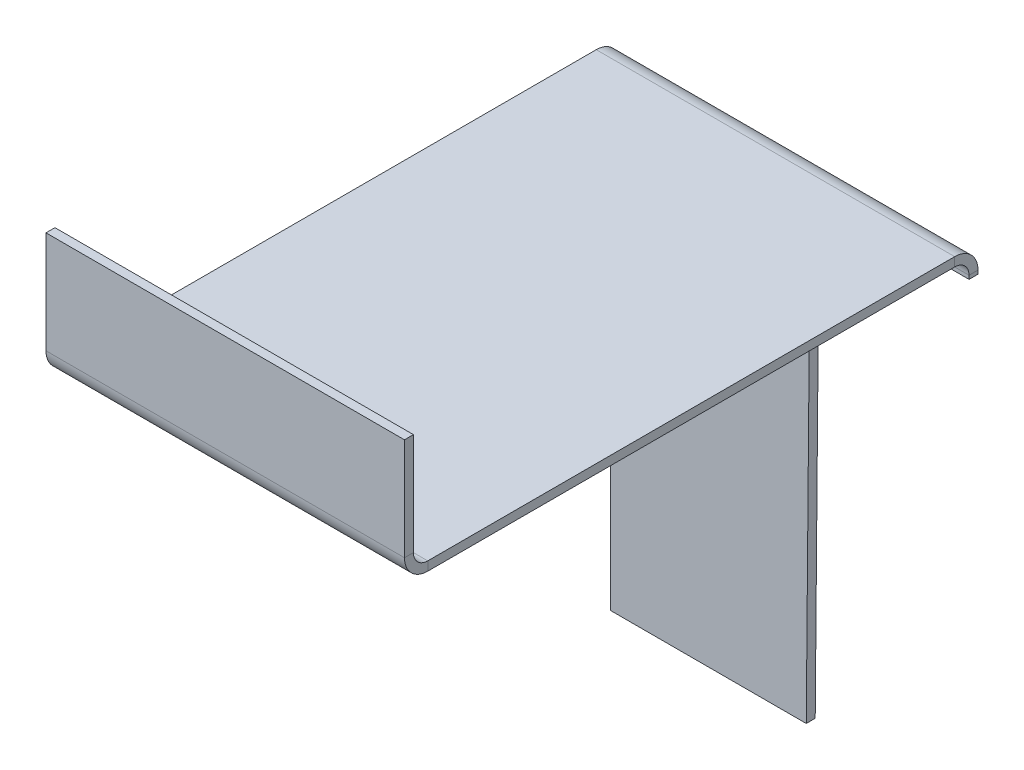
SolidWorks part; units mm, degrees
note: The reader was unsure of these and kept them because the rebuilt part matched: flange length of "Edge-Flange1", "Edge-Flange2".
material "Plain Carbon Steel"
ref_plane "Front Plane" through (0, 0, 0) normal (0, 0, 1) x (1, 0, 0)
ref_plane "Top Plane" through (0, 0, 0) normal (0, 1, 0) x (1, 0, 0)
ref_plane "Right Plane" through (0, 0, 0) normal (1, 0, 0) x (0, 0, -1)
sketch "Sketch1" plane through (0, 0, 0) normal (0, 0, 1) x (1, 0, 0)
  line L0 (0, 0) -> (0, 3)
  line L1 (0, 3) -> (-40, 3)
  line L2 (0, 0) -> (-17.7, 0)
  line L3 (-17.7, 0) -> (-18.1651, -52)
  line L4 (-40, 3) -> (-40, -52)
  line L5 (-40, -52) -> (-18.1651, -52)
  dimension "D1" = 3
  dimension "D2" = 40
  dimension "D3" = 17.7
  dimension "D4" = 55
base flange "Base-Flange1" sketch "Sketch1" thickness 1 reverse thickness direction no parameters "D1"=1.6
edge flange "Edge-Flange1" sketch "Sketch8" flange angle 90 flange length 64 flange position material inside bend radius 1.6 thickness 1 relief rectangular parameters "D6"=10
sketch "Sketch8" plane through (0, 3, 0) normal (0, 1, 0) x (-1, 0, 0)
  line L0 (0, 0) -> (40, 0) construction
  line L1 (0, 0) -> (40, 0)
  line L2 (0, 0) -> (0, 63)
  line L3 (0, 63) -> (40, 63)
  line L4 (40, 63) -> (40, 0)
bend "EdgeBend1" bend radius 1.6 bend angle 90 parameters "D5"=1
edge flange "Edge-Flange2" sketch "Sketch11" flange angle 90 flange length 14 flange position material inside bend radius 1.6 thickness 1 relief rectangular parameters "D6"=10
sketch "Sketch11" plane through (0, 3, 63) normal (0, 0, 1) x (1, 0, 0)
  line L0 (-40, 0) -> (0, 0) construction
  line L1 (-40, 0) -> (0, 0)
  line L2 (-40, 0) -> (-40, 13)
  line L3 (-40, 13) -> (0, 13)
  line L4 (0, 13) -> (0, 0)
bend "EdgeBend2" bend radius 1.6 bend angle 90 parameters "D5"=2
sketch "Bend-Lines1" [suppressed] plane through (0, 0, 0) normal (0, 1, 0) x (1, 0, 0)
sketch "Bounding-Box1" [suppressed] plane through (0, 0, 0) normal (0, 1, 0) x (1, 0, 0)
sheet metal parameters "Sheet-Metal8" thickness 1 parameters "D1"=1.6
flat pattern "Flat-Pattern8" [suppressed]
sketch "Bend-Lines2" plane through (0, 0, 0) normal (0, 1, 0) x (1, 0, 0)
sketch3d "Bounding-Box2" [suppressed]
  line L0 (0, 3, 0) -> (0, -52, 0) construction
  line L1 (40, 3, 0) -> (40, -52, 0) construction
  line L2 (0, 3, 0) -> (40, 3, 0) construction
  line L3 (0, -52, 0) -> (40, -52, 0) construction
sheet metal parameters "Sheet-Metal9" thickness 1 parameters "D1"=1.6
flat pattern "Flat-Pattern8"
sketch "Bend-Lines2" plane through (0, 0, 0) normal (0, 0, 1) x (1, 0, 0)
  line L0 (0, 2.0493) -> (-40, 2.0493) construction
  line L1 (0, 2.0493) -> (-40, 2.0493) construction
sketch3d "Bounding-Box2" [suppressed]
  line L0 (0, 65.0987, 0) -> (0, -52, 0) construction
  line L1 (-40, 65.0987, 0) -> (-40, -52, 0) construction
  line L2 (0, 65.0987, 0) -> (-40, 65.0987, 0) construction
  line L3 (0, -52, 0) -> (-40, -52, 0) construction
bend of the flat pattern "Flatten-<EdgeBend1>1"
sheet metal parameters "Sheet-Metal10" thickness 1 parameters "D1"=1.6
flat pattern "Flat-Pattern8"
sketch "Bend-Lines2" plane through (0, 0, 0) normal (0, 0, 1) x (1, 0, 0)
  line L0 (0, 2.0493) -> (-40, 2.0493) construction
  line L1 (0, 2.0493) -> (-40, 2.0493) construction
  line L2 (0, 64.148) -> (-40, 64.148) construction
  line L3 (0, 64.148) -> (-40, 64.148) construction
sketch3d "Bounding-Box2" [suppressed]
  line L0 (0, 77.1973, 0) -> (0, -52, 0) construction
  line L1 (-40, 77.1973, 0) -> (-40, -52, 0) construction
  line L2 (0, 77.1973, 0) -> (-40, 77.1973, 0) construction
  line L3 (0, -52, 0) -> (-40, -52, 0) construction
bend of the flat pattern "Flatten-<EdgeBend1>1"
bend of the flat pattern "Flatten-<EdgeBend2>1"
